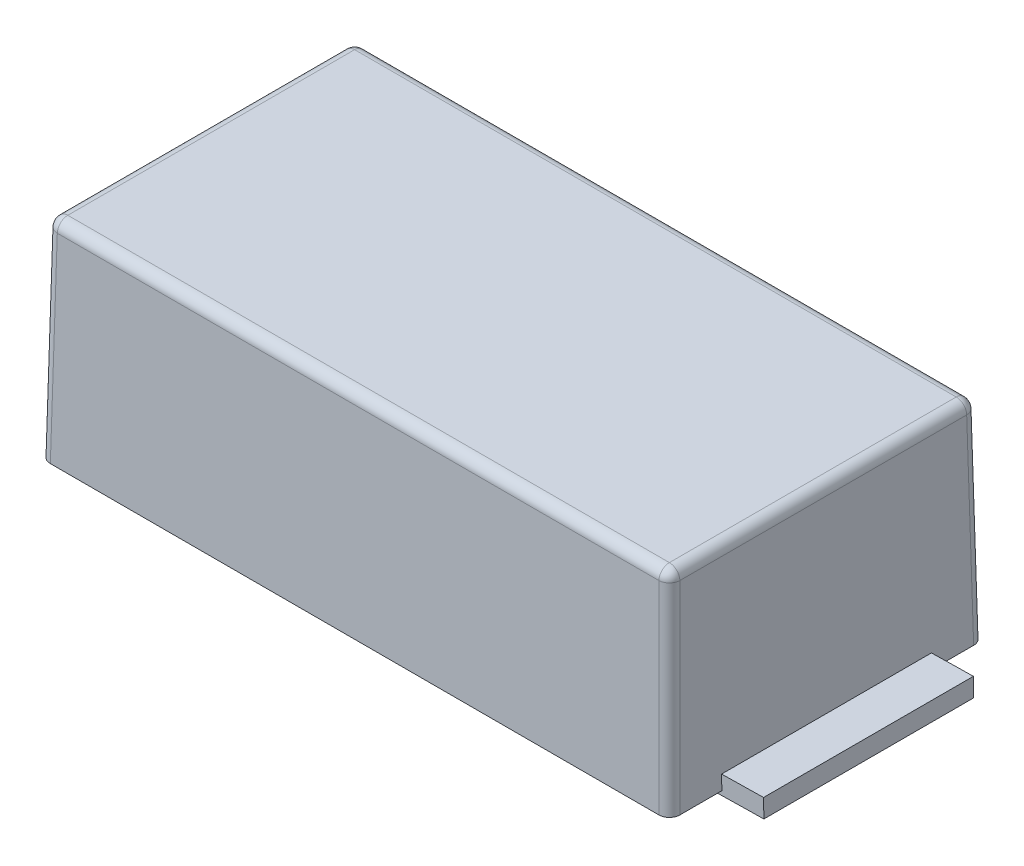
SolidWorks part; units mm, degrees
ref_plane "Front Plane" through (0, 0, 0) normal (0, 0, 1) x (1, 0, 0)
ref_plane "Top Plane" through (0, 0, 0) normal (0, 1, 0) x (1, 0, 0)
ref_plane "Right Plane" through (0, 0, 0) normal (1, 0, 0) x (0, 0, -1)
sketch "Sketch1" plane through (0, 0, 0) normal (0, 1, 0) x (1, 0, 0)
  line L1 (-1.5, -0.75) -> (1.5, -0.75)
  line L2 (-1.5, -0.75) -> (-1.5, 0.75)
  line L3 (-1.5, 0.75) -> (1.5, 0.75)
  line L4 (1.5, -0.75) -> (1.5, 0.75)
  line L5 (-1.5, -0.75) -> (1.5, 0.75) construction
  line L6 (-1.5, 0.75) -> (1.5, -0.75) construction
  point P0 (0, 0)
  dimension "D1" = 3
  dimension "D2" = 1.5
extrude "Boss-Extrude1" add sketch "Sketch1" along normal blind 1
chamfer "Chamfer1" distance 1 angle 1 4 edges at (-1.5, 1, 0) (0, 1, -0.75) (1.5, 1, 0) (0, 1, 0.75) first distance on face at (-1.5, 0.5, 0) first distance on face at (0, 0.5, -0.75) first distance on face at (1.5, 0.5, 0) first distance on face at (0, 0.5, 0.75)
fillet "Fillet1" radius 0.05 8 edges at (1.4825, 1, 0) (0, 1, 0.7325) (-1.4825, 1, 0) (0, 1, -0.7325) (-1.4913, 0.5, 0.7413) (-1.4913, 0.5, -0.7413) (1.4913, 0.5, -0.7413) (1.4913, 0.5, 0.7413)
sketch "Sketch2" plane through (1.4995, 0.0262, 0) normal (0.9998, 0.0175, 0) x (0, 0, -1)
  line L0 (-0.7, -0.0262) -> (0.7, -0.0262) construction
  line L1 (-0.5, 0.042) -> (0.5, 0.042)
  line L2 (-0.5, 0.042) -> (-0.5, -0.0462)
  line L3 (-0.5, -0.0462) -> (0.5, -0.0462)
  line L4 (0.5, 0.042) -> (0.5, -0.0462)
  dimension "D1" = 1
  dimension "D2" = 0.25
  dimension "D3" = 0.02
extrude "Boss-Extrude2" add sketch "Sketch2" along normal blind 0.2 and the other way blind 0.5
mirror "Mirror1" about plane through (0, 0, 0) normal (1, 0, 0) of "Boss-Extrude2"
